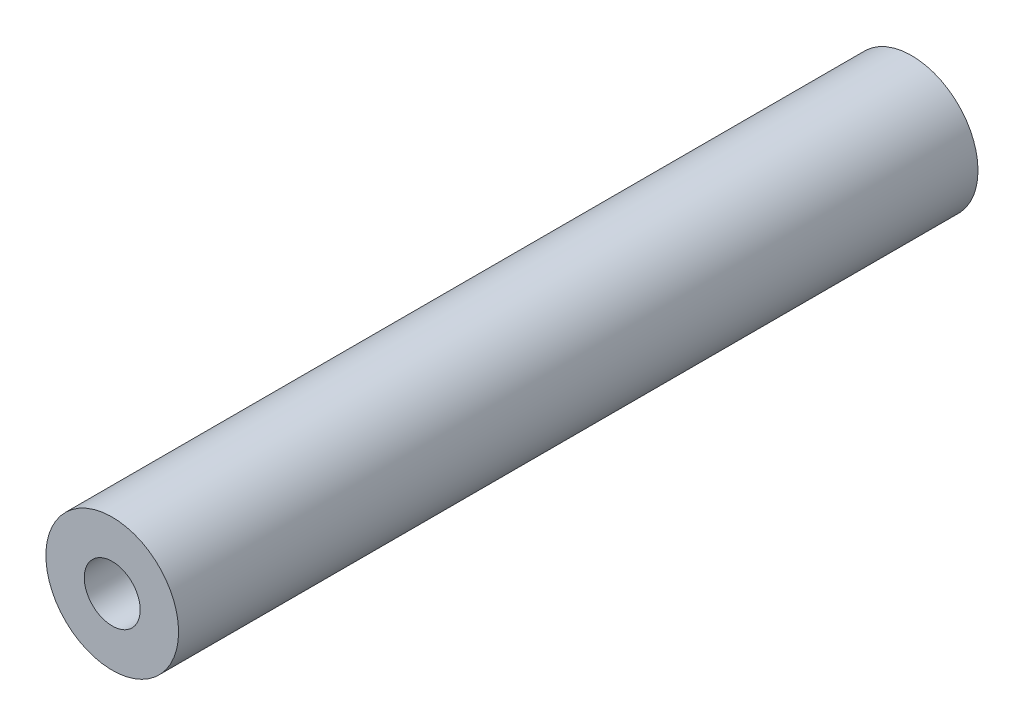
SolidWorks part; units mm, degrees
ref_plane "Спереди" through (0, 0, 0) normal (0, 0, 1) x (1, 0, 0)
ref_plane "Сверху" through (0, 0, 0) normal (0, 1, 0) x (1, 0, 0)
ref_plane "Справа" through (0, 0, 0) normal (1, 0, 0) x (0, 0, -1)
sketch "Эскиз1" plane through (0, 0, 0) normal (0, 0, 1) x (1, 0, 0)
  circle A0 centre (0, 0) radius 2.075
  circle A1 centre (0, 0) radius 0.875
extrude "Бобышка-Вытянуть1" add sketch "Эскиз1" along normal blind 12.5 and the other way blind 12.5
sketch "Эскиз2" plane through (0, 0, 0) normal (0, 0, 1) x (1, 0, 0)
  circle A0 centre (0, 0) radius 0.875
  circle A1 centre (0, 0) radius 0.4375
extrude "Бобышка-Вытянуть2" add sketch "Эскиз2" along normal blind 2 and the other way blind 2 separate body
